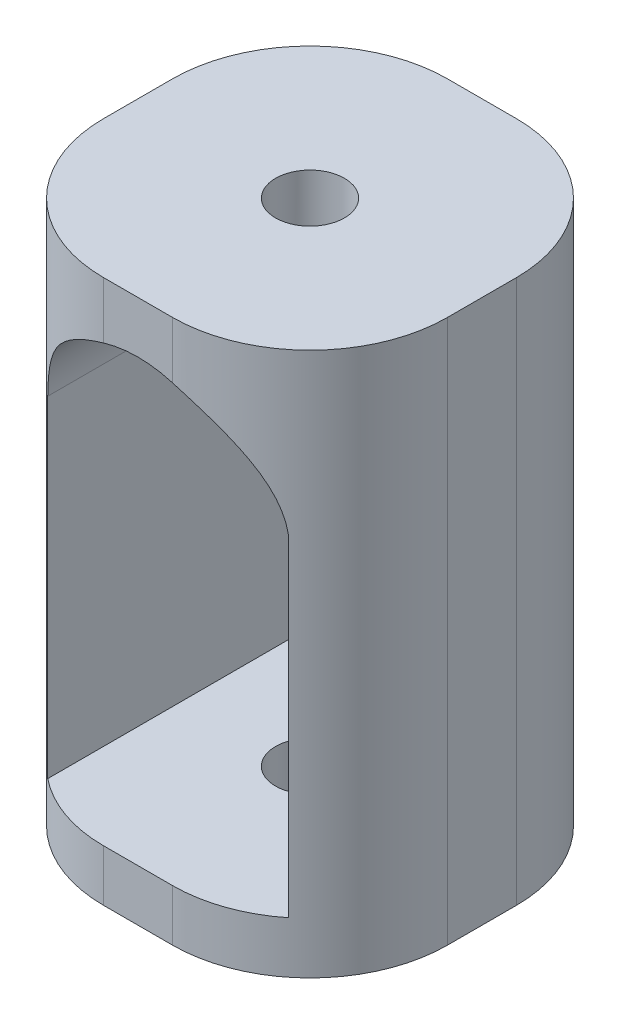
SolidWorks part; units mm, degrees
ref_plane "Alzado" through (0, 0, 0) normal (0, 0, 1) x (1, 0, 0)
ref_plane "Planta" through (0, 0, 0) normal (0, 1, 0) x (1, 0, 0)
ref_plane "Vista lateral" through (0, 0, 0) normal (1, 0, 0) x (0, 0, -1)
sketch "Croquis1" plane through (0, 0, 0) normal (0, 1, 0) x (1, 0, 0)
  line L1 (0, 0) -> (-20, 0)
  line L2 (0, 0) -> (0, -20)
  line L3 (0, -20) -> (-20, -20)
  line L4 (-20, 0) -> (-20, -20)
  dimension "D1" = 20
  dimension "D2" = 20
extrude "Saliente-Extruir1" add sketch "Croquis1" along normal blind 30
sketch "Croquis3" plane through (0, 0, 20) normal (0, 0, 1) x (1, 0, 0)
  line L0 (-16.65, 8.7) -> (-20, 8.7) construction
  line L2 (-16.65, 8.7) -> (-16.65, 7.4) construction
  line L3 (-16.65, 7.4) -> (-3.35, 7.4) construction
  line L4 (-3.35, 8.7) -> (-3.35, 7.4) construction
  line L5 (-20, 30) -> (-20, 0) construction
  line L6 (-3.35, 8.7) -> (0, 8.7) construction
  line L7 (0, 30) -> (0, 0) construction
  line L8 (-10, 7.4) -> (-10, 20.1) construction
  line L10 (-10, 20.1) -> (-10, 25.1) construction
  circle A0 centre (-10, 13.75) radius 6.35
  dimension "D4" = 5
  dimension "D1" = 12.7
  dimension "D2" = 13.3
  dimension "D3" = 3.35
extrude "Cortar-Extruir1" cut sketch "Croquis3" against normal blind 18
sketch "Croquis4" plane through (0, 30, 0) normal (0, 1, 0) x (1, 0, 0)
  line L0 (-10, -10) -> (-10, 0) construction
  line L1 (0, 0) -> (-20, 0) construction
  line L2 (-10, -10) -> (0, -10) construction
  line L3 (0, -20) -> (0, 0) construction
  circle A0 centre (-10, -10) radius 2
  dimension "D1" = 4
  dimension "D2" = 10
extrude "Cortar-Extruir2" cut sketch "Croquis4" against normal up to surface (30 mm away) up to face at (-10, 0, 10)
sketch "Croquis7" plane through (0, 0, 0) normal (0, -1, 0) x (1, 0, 0)
  line L8 (0, 0) -> (0, 20)
  line L9 (0, 20) -> (-20, 20)
  line L10 (-20, 20) -> (-20, 0)
  line L11 (-20, 0) -> (0, 0)
  line L12 (0, 0) -> (0, 20)
  line L13 (0, 20) -> (-20, 20)
  line L14 (-20, 20) -> (-20, 0)
  line L15 (-20, 0) -> (0, 0)
  circle A0 centre (-10, 10) radius 2 construction
  circle A1 centre (-10, 10) radius 2
  dimension "D1" = 0
extrude "Saliente-Extruir3" add sketch "Croquis7" along normal blind 1.6
sketch "Croquis8" plane through (0, 0, 20) normal (0, 0, 1) x (1, 0, 0)
  line L0 (-10, 30) -> (-10, 27) construction
  line L1 (-20, 30) -> (0, 30) construction
  line L2 (-10, -1.6) -> (-10, 1.4) construction
  line L3 (-17, 7.75) -> (-17, 1.4)
  line L4 (0, -1.6) -> (-20, -1.6) construction
  line L5 (-3, 27) -> (-17, 27) construction
  line L6 (-17, 27) -> (-17, 20.65) construction
  line L7 (-20, 14.2) -> (-18.3764, 14.2) construction
  line L8 (-20, 30) -> (-20, -1.6) construction
  line L9 (-3, 27) -> (-3, 20.65) construction
  line L10 (-17, 20.65) -> (-17, 7.75)
  line L11 (-3, 20.65) -> (-3, 7.75)
  line L12 (-17, 1.4) -> (-3, 1.4)
  line L13 (-3, 1.4) -> (-3, 7.75)
  arc A0 (-17, 20.65) -> (-3, 20.65) centre (-10, 19.9667) cw
  dimension "D1" = 3
  dimension "D2" = 3
  dimension "D3" = 6.35
  dimension "D4" = 7
extrude "Cortar-Extruir3" cut sketch "Croquis8" against normal up to next
fillet "Redondeo1" radius 8 4 edges at (-20, 14.2, 0) (0, 14.2, 0) (-20, 14.2, 20) (0, 14.2, 20)
